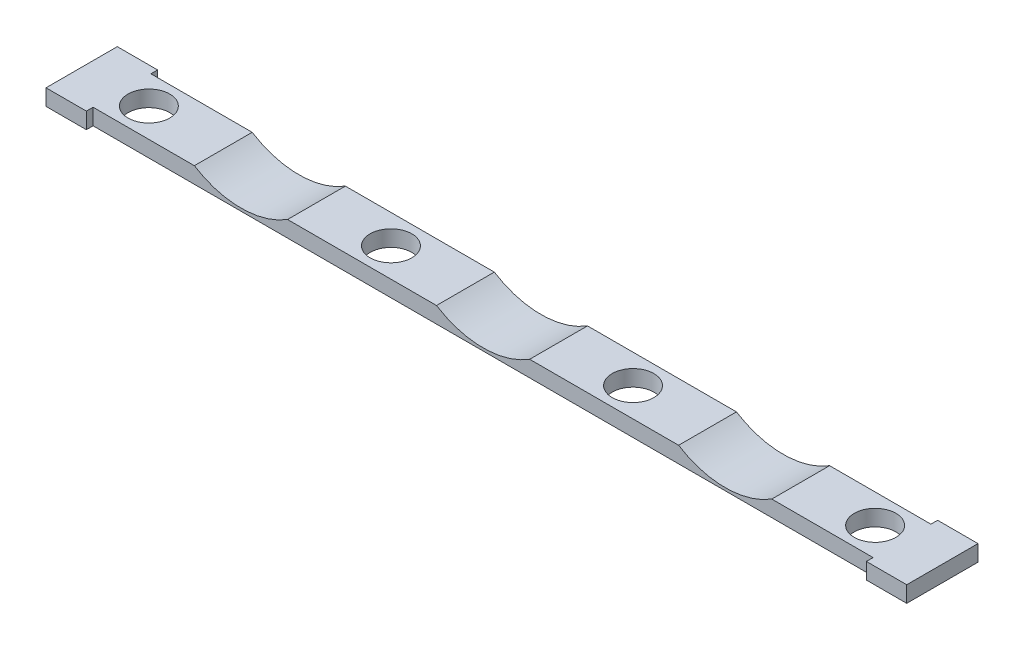
SolidWorks part; units mm, degrees
ref_plane "Front Plane" through (0, 0, 0) normal (0, 0, 1) x (1, 0, 0)
ref_plane "Top Plane" through (0, 0, 0) normal (0, 1, 0) x (1, 0, 0)
ref_plane "Right Plane" through (0, 0, 0) normal (1, 0, 0) x (0, 0, -1)
sketch "Sketch1" plane through (0, 0, 0) normal (0, 0, 1) x (1, 0, 0)
  line L0 (-18.0028, 6) -> (-18.0028, -6) construction
  line L1 (-11.5028, 6) -> (-11.5028, -6) construction
  line L2 (-24.5028, 6) -> (-24.5028, -6) construction
  line L3 (0, 6) -> (0, -6) construction
  line L4 (6.5, 6) -> (6.5, -6) construction
  line L5 (-6.5, 6) -> (-6.5, -6) construction
  line L6 (18.0028, 6) -> (18.0028, -6) construction
  line L7 (24.5028, 6) -> (24.5028, -6) construction
  line L8 (11.5028, 6) -> (11.5028, -6) construction
  line L13 (-18.0028, 6.35) -> (-18.0028, -6.35) construction
  line L18 (-14.5387, -11.5) -> (-3.4641, -11.5)
  line L19 (3.4641, -11.5) -> (14.5387, -11.5)
  line L20 (-15.9528, 6.35) -> (-15.9528, -6.35) construction
  line L21 (-20.0528, 6.35) -> (-20.0528, -6.35) construction
  line L22 (-0.0028, 6.35) -> (-0.0028, -6.35) construction
  line L23 (2.0472, 6.35) -> (2.0472, -6.35) construction
  line L24 (-2.0528, 6.35) -> (-2.0528, -6.35) construction
  line L25 (17.9972, 6.35) -> (17.9972, -6.35) construction
  line L26 (20.0472, 6.35) -> (20.0472, -6.35) construction
  line L27 (15.9472, 6.35) -> (15.9472, -6.35) construction
  line L30 (-32, -12.7) -> (32, -12.7)
  line L31 (-21.4669, -11.5) -> (-32, -11.5)
  line L32 (-32, -11.5) -> (-32, -12.7)
  line L33 (21.4669, -11.5) -> (32, -11.5)
  line L34 (32, -11.5) -> (32, -12.7)
  line L35 (-9.0014, -11.5) -> (-9.0014, 6) construction
  line L36 (9.0014, -11.5) -> (9.0014, 6) construction
  line L37 (27.0014, -11.5) -> (27.0014, 6) construction
  line L38 (-27.0014, -11.5) -> (-27.0014, 6) construction
  arc A0 (-11.5028, 6) -> (-24.5028, 6) centre (-18.0028, 6) ccw construction
  arc A1 (-24.5028, -6) -> (-11.5028, -6) centre (-18.0028, -6) ccw construction
  arc A2 (6.5, 6) -> (-6.5, 6) centre (0, 6) ccw construction
  arc A3 (-6.5, -6) -> (6.5, -6) centre (0, -6) ccw construction
  arc A4 (24.5028, 6) -> (11.5028, 6) centre (18.0028, 6) ccw construction
  arc A5 (11.5028, -6) -> (24.5028, -6) centre (18.0028, -6) ccw construction
  arc A8 (-15.9528, 6.35) -> (-20.0528, 6.35) centre (-18.0028, 6.35) ccw construction
  arc A9 (-20.0528, -6.35) -> (-15.9528, -6.35) centre (-18.0028, -6.35) ccw construction
  arc A10 (2.0472, 6.35) -> (-2.0528, 6.35) centre (-0.0028, 6.35) ccw construction
  arc A11 (-2.0528, -6.35) -> (2.0472, -6.35) centre (-0.0028, -6.35) ccw construction
  arc A12 (20.0472, 6.35) -> (15.9472, 6.35) centre (17.9972, 6.35) ccw construction
  arc A13 (15.9472, -6.35) -> (20.0472, -6.35) centre (17.9972, -6.35) ccw construction
  arc A14 (-21.4669, -11.5) -> (-14.5387, -11.5) centre (-18.0028, -6) ccw
  arc A15 (-3.4641, -11.5) -> (3.4641, -11.5) centre (0, -6) ccw
  arc A16 (14.5387, -11.5) -> (21.4669, -11.5) centre (18.0028, -6) ccw
  arc A17 (-9.0014, 6) -> (-27.0014, 6) centre (-18.0014, 6) ccw construction
  arc A18 (9.0014, 6) -> (27.0014, 6) centre (18.0014, 6) cw construction
  point P3 (-18.0028, 0)
  point P11 (0, 0)
  point P18 (18.0028, 0)
  point P24 (0, 0)
  point P38 (-18.0028, 0)
  point P47 (-0.0028, 0)
  point P54 (17.9972, 0)
  point P59 (-18.0028, -12.5)
  dimension "D3" = 3
  dimension "D1" = 13
  dimension "D2" = 12
  dimension "D4" = 11.5
  dimension "D5" = 18.0028
  dimension "D6" = 0.2
  dimension "D7" = 18
  dimension "D8" = 18
  dimension "D9" = 64
  dimension "D11" = 4.1
  dimension "D12" = 12.7
  dimension "D13" = 3
extrude "Boss-Extrude1" add sketch "Sketch1" along normal blind 4.3
sketch "Sketch2" plane through (0, -11.5, 0) normal (0, 1, 0) x (1, 0, 0)
  line L0 (-32, -2.15) -> (32, -2.15) construction
  line L1 (-32, -4.3) -> (-32, 0) construction
  line L2 (32, -4.3) -> (32, 0) construction
  line L3 (0, 0) -> (0, -4.3) construction
  line L4 (-3.4641, -4.3) -> (3.4641, -4.3) construction
  circle A0 centre (-9, -2.15) radius 1.55
  circle A1 centre (9, -2.15) radius 1.55
  circle A2 centre (-27, -2.15) radius 1.55
  circle A3 centre (27, -2.15) radius 1.55
  dimension "D1" = 3.1
  dimension "D2" = 18
  dimension "D3" = 9
  dimension "D4" = 9
  dimension "D5" = 18
extrude "Cut-Extrude1" cut sketch "Sketch2" against normal through all
ref_plane "Plane1" through (0, 0, 2.15) normal (0, 0, -1) x (-1, 0, 0)
sketch "Sketch3" plane through (0, 0, 0) normal (0, 0, -1) x (-1, 0, 0)
  line L0 (32, -12.7) -> (-32, -12.7) construction
  line L1 (-32, -11.5) -> (-29, -11.5)
  line L2 (-32, -11.5) -> (-32, -12.7)
  line L3 (-32, -12.7) -> (-29, -12.7)
  line L4 (-29, -11.5) -> (-29, -12.7)
  line L6 (32, -11.5) -> (29, -11.5)
  line L7 (32, -11.5) -> (32, -12.7)
  line L8 (32, -12.7) -> (29, -12.7)
  line L9 (29, -11.5) -> (29, -12.7)
  dimension "D1" = 3
  dimension "D2" = 3
extrude "Boss-Extrude2" add sketch "Sketch3" along normal blind 0.5
mirror "Mirror1" about plane through (0, 0, 2.15) normal (0, 0, -1) of "Boss-Extrude2"
